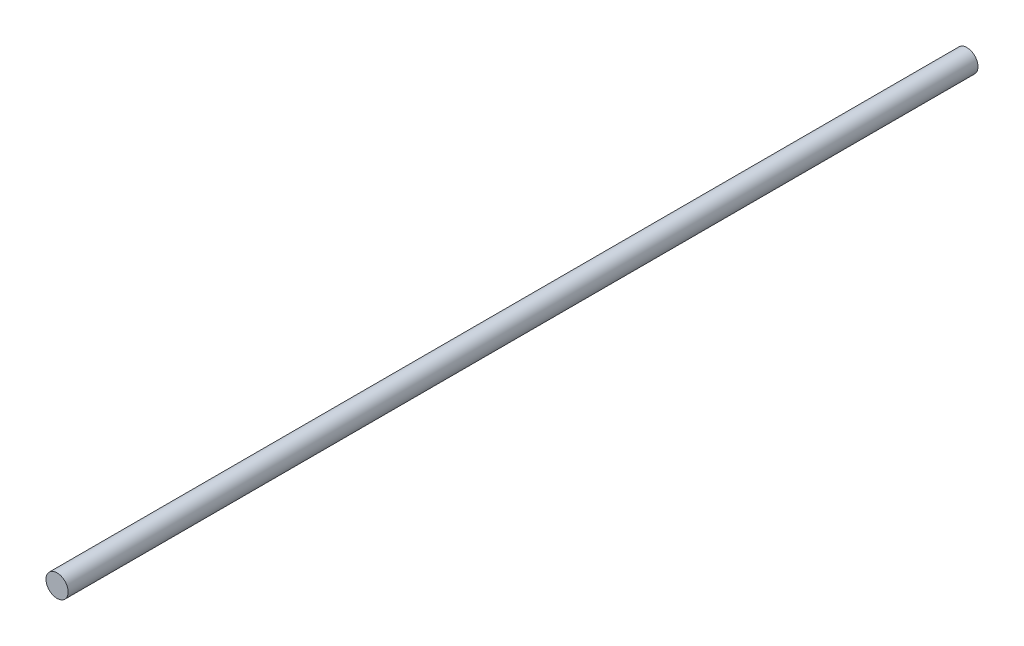
SolidWorks part; units mm, degrees
ref_plane "Front Plane" through (0, 0, 0) normal (0, 0, 1) x (1, 0, 0)
ref_plane "Top Plane" through (0, 0, 0) normal (0, 1, 0) x (1, 0, 0)
ref_plane "Right Plane" through (0, 0, 0) normal (1, 0, 0) x (0, 0, -1)
sketch "Sketch1" plane through (0, 0, 0) normal (0, 0, 1) x (1, 0, 0)
  circle A0 centre (0, 0) radius 4.953
  dimension "D1" = 9.906
extrude "Boss-Extrude1" add sketch "Sketch1" along normal blind 203.2 and the other way blind 203.2
